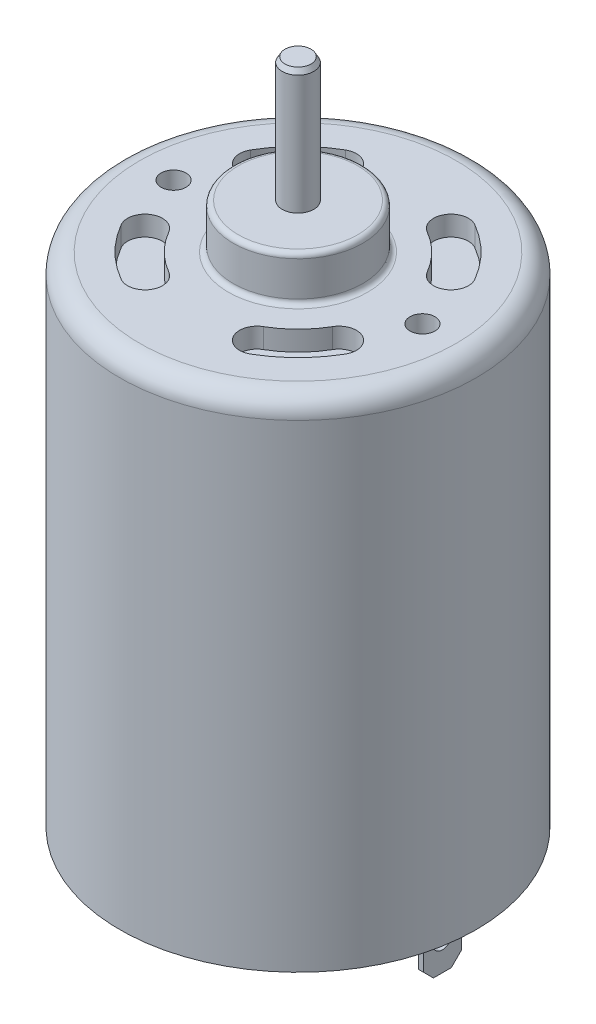
SolidWorks part; units mm, degrees
material "6061 Alloy"
ref_plane "Front Plane" through (0, 0, 0) normal (0, 0, 1) x (1, 0, 0)
ref_plane "Top Plane" through (0, 0, 0) normal (0, 1, 0) x (1, 0, 0)
ref_plane "Right Plane" through (0, 0, 0) normal (1, 0, 0) x (0, 0, -1)
sketch "Sketch1" plane through (0, 0, 0) normal (0, 0, 1) x (1, 0, 0)
  line L0 (0, 42) -> (0, -34.0742) construction
  line L1 (0, 42) -> (1.5875, 42)
  line L2 (1.5875, 42) -> (1.5875, 29.5)
  line L3 (1.5875, 29.5) -> (6.5, 29.5)
  line L4 (6.5, 29.5) -> (6.5, 25)
  line L5 (6.5, 25) -> (17.9, 25)
  line L6 (17.9, 25) -> (17.9, -25)
  line L7 (1.5875, -29) -> (1.5875, -28)
  line L9 (0, 42) -> (0, -29)
  line L11 (17.9, -25) -> (16.855, -25)
  line L12 (16.855, -25) -> (16.855, -23.25)
  line L13 (16.855, -23.25) -> (11.725, -23.25)
  line L14 (11.725, -23.25) -> (11.725, -23.87)
  line L15 (11.725, -23.87) -> (5.1, -23.87)
  line L16 (5.1, -23.87) -> (5.1, -28)
  line L17 (5.1, -28) -> (1.5875, -28)
  line L21 (1.5875, -29) -> (0, -29)
  line L23 (0, 0) -> (17.13, 0) construction
  dimension "D2" = 6.5
  dimension "D3" = 4.5
  dimension "D4" = 17.9
  dimension "D5" = 1.5875
  dimension "D6" = 5.1
  dimension "D7" = 1.5875
  dimension "D8" = 1.75
  dimension "D9" = 5.13
  dimension "D10" = 17
  dimension "D11" = 0.62
  dimension "D12" = 6.625
  dimension "D13" = 3
  dimension "D14" = 25
  dimension "D15" = 71
  dimension "D18" = 50
revolve "Revolve1" add sketch "Sketch1" angle 360 about L0
sketch "Sketch3" plane through (0, 25, 0) normal (0, 1, 0) x (1, 0, 0)
  line L0 (0, 0) -> (0, 17.9) construction
  circle A0 centre (12.5, 0) radius 1.25
  circle A1 centre (0, 0) radius 6.5 construction
  circle A2 centre (0, 0) radius 17.9 construction
  circle A3 centre (-12.5, 0) radius 1.25
  dimension "D1" = 2.5
  dimension "D2" = 12.5
extrude "Cut-Extrude2" cut sketch "Sketch3" against normal blind 5
sketch "Sketch4" plane through (0, 25, 0) normal (0, 1, 0) x (1, 0, 0)
  line L0 (8.2272, 4.75) -> (11.2583, 6.5)
  line L1 (6.5, 11.2583) -> (4.75, 8.2272)
  arc A0 (11.2583, 6.5) -> (6.5, 11.2583) centre (0, 0) ccw
  arc A1 (8.2272, 4.75) -> (4.75, 8.2272) centre (0, 0) ccw
  arc A2 (4.75, 8.2272) -> (6.5, 11.2583) centre (5.625, 9.7428) cw
  arc A3 (8.2272, 4.75) -> (11.2583, 6.5) centre (9.7428, 5.625) ccw
  point P3 (0, 0)
  dimension "D1" = 9.5
  dimension "D2" = 13
  dimension "D3" = 30
extrude "Cut-Extrude3" cut sketch "Sketch4" against normal blind 2 contours A2 L1 | A1 L0 A0 L1 | L0 A3 region at (7.9278, 25, -7.9278) region at (10.1141, 25, -4.9818) region at (4.9818, 25, -10.1141)
pattern_circular "CirPattern1" count 4 over 360 about axis through (0, 42, 0) along (0, -1, 0) of "Cut-Extrude3"
sketch "Sketch5" plane through (0, -23.87, 0) normal (0, -1, 0) x (1, 0, 0)
  line L0 (3.15, 9.3591) -> (3.15, 5.6857)
  line L1 (5.6857, 3.15) -> (9.3591, 3.15)
  arc A0 (5.6857, 3.15) -> (3.15, 5.6857) centre (0, 0) ccw
  arc A1 (9.3591, 3.15) -> (3.15, 9.3591) centre (0, 0) ccw
  point P4 (0, 0)
extrude "Cut-Extrude4" cut sketch "Sketch5" against normal blind 1
pattern_circular "CirPattern2" count 4 over 360 about axis through (0, 23, 0) along (0, 1, 0) of "Cut-Extrude4"
ref_plane "Plane4" through (14, 0, 0) normal (1, 0, 0) x (0, 0, -1)
sketch "Sketch6" plane through (14, 0, 0) normal (1, 0, 0) x (0, 0, -1)
  line L0 (-16.855, -23.25) -> (16.855, -23.25) construction
  line L1 (-1.9, -23.25) -> (1.9, -23.25)
  line L2 (-1.9, -23.25) -> (-1.9, -30.45)
  line L3 (-1.9, -30.45) -> (1.9, -30.45)
  line L4 (1.9, -23.25) -> (1.9, -30.45)
  line L5 (0, 0) -> (0, -40.6119) construction
  circle A0 centre (0, -27.45) radius 1
  dimension "D3" = 4.2
  dimension "D4" = 2
  dimension "D1" = 3.8
  dimension "D2" = 7.2
extrude "Extrude1" add sketch "Sketch6" along normal blind 0.5
mirror "Mirror1" about plane through (0, 0, 0) normal (1, 0, 0) of "Extrude1"
chamfer "Chamfer1" distance 1 angle 45 4 edges at (-14.25, -30.45, 1.9) (-14.25, -30.45, -1.9) (14.25, -30.45, 1.9) (14.25, -30.45, -1.9)
fillet "Fillet1" radius 2 1 edges at (-17.9, 25, 0)
fillet "Fillet3" radius 0.5 2 edges at (-6.5, 25, 0) (-6.5, 29.5, 0)
chamfer "Chamfer2" distance 0.5 angle 30 2 edges at (-1.5875, 42, 0) (-1.5875, -29, 0) first distance on face at (-1.5875, 42, 0) first distance on face at (-1.5875, -29, 0)
ref_axis "Axis1" through (12.5, 20, 0) along (0, 1, 0)
